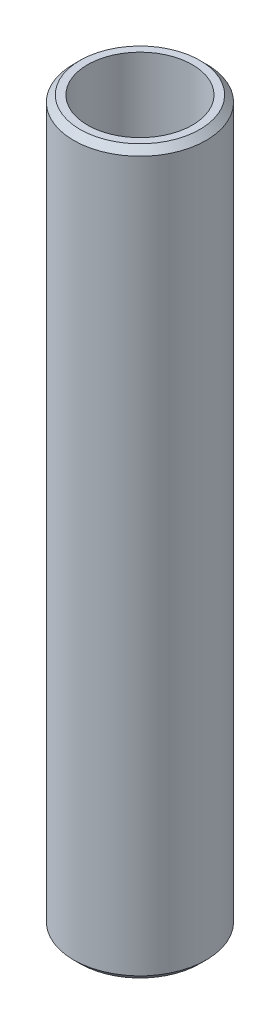
SolidWorks part; units mm, degrees
ref_plane "Front Plane" through (0, 0, 0) normal (0, 0, 1) x (1, 0, 0)
ref_plane "Top Plane" through (0, 0, 0) normal (0, 1, 0) x (1, 0, 0)
ref_plane "Right Plane" through (0, 0, 0) normal (1, 0, 0) x (0, 0, -1)
sketch "Sketch1" plane through (0, 0, 0) normal (0, 1, 0) x (1, 0, 0)
  circle A0 centre (0, 0) radius 55
  dimension "SHAFT_OD" = 110
extrude "Boss-Extrude1" add sketch "Sketch1" along normal blind 600
sketch "Sketch2" plane through (0, 0, 0) normal (0, 1, 0) x (1, 0, 0)
  circle A0 centre (0, 0) radius 43.5171
  dimension "BORE_D" = 87.0341
extrude "Cut-Extrude1" cut sketch "Sketch2" along normal through all
chamfer "Chamfer1" distance 5.2618 angle 45 2 edges at (0, 600, 55) (0, 0, 55)
